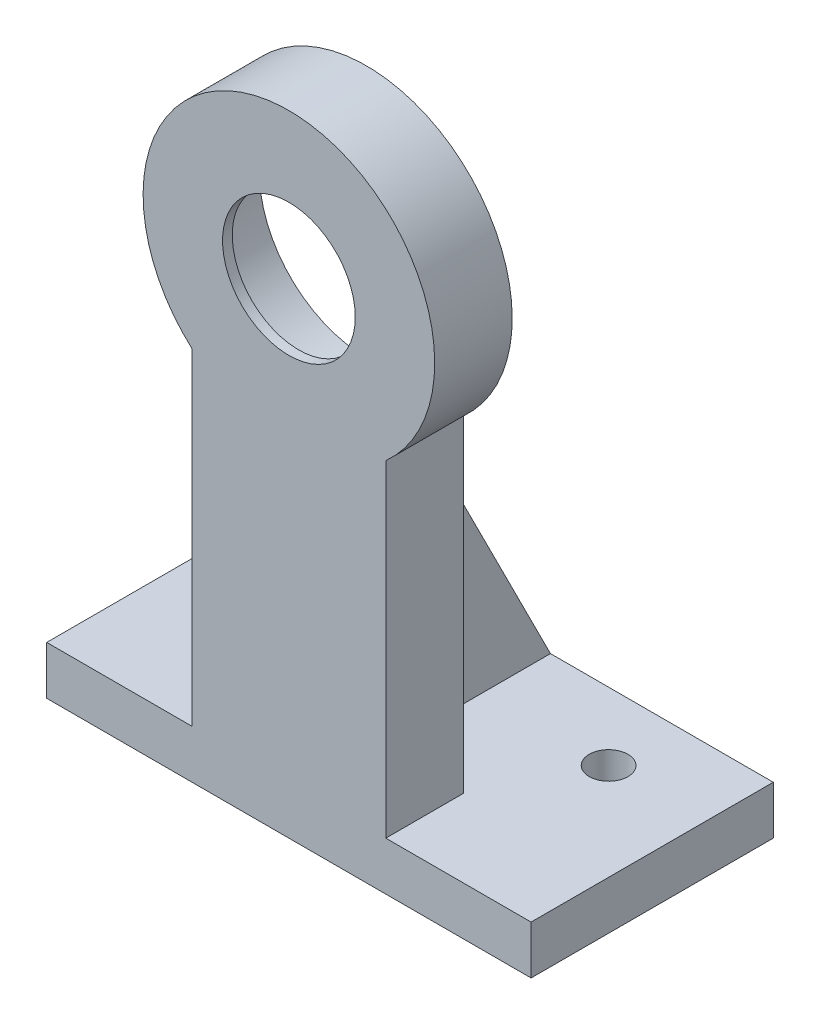
SolidWorks part; units mm, degrees
ref_plane "Front Plane" through (0, 0, 0) normal (0, 0, 1) x (1, 0, 0)
ref_plane "Top Plane" through (0, 0, 0) normal (0, 1, 0) x (1, 0, 0)
ref_plane "Right Plane" through (0, 0, 0) normal (1, 0, 0) x (0, 0, -1)
sketch "Sketch1" plane through (0, 0, 0) normal (0, 0, 1) x (1, 0, 0)
  line L1 (-10, 0) -> (10, 0)
  line L2 (-10, 0) -> (-10, -50)
  line L3 (-10, -50) -> (10, -50)
  line L4 (10, 0) -> (10, -50)
  circle A0 centre (0, 0) radius 11.05
  circle A1 centre (0, 0) radius 6.848
  circle A2 centre (0, 0) radius 15.05
  point P9 (0, 0)
  dimension "D1" = 22.1
  dimension "D2" = 13.6959
  dimension "D3" = 4
  dimension "D4" = 20
  dimension "D5" = 0
  dimension "D6" = 50
extrude "Boss-Extrude1" add sketch "Sketch1" along normal blind 8 contours A2 L2 L3 L4 | L4 A2 L2 A0 | L2 A2 L4 A0 | A1 L1 L2 A0 L4 | A1 L1 L4 A0 L2 region at (0, 7.1194, 0) region at (8.424, -0.2285, 0) region at (11.1744, -2.4957, 0) region at (0, -11.3558, 0) region at (0, -31.9102, 0)
extrude "Cut-Extrude1" cut sketch "Sketch1<3>" along normal blind 7 contours A1 L1 L4 A0 L2 | A1 L1 L2 A0 L4 region at (0, 7.1194, 0) region at (8.424, -0.2285, 0)
sketch "Sketch1<3>" plane through (0, 0, 0) normal (0, 0, 1) x (1, 0, 0) same geometry as "Sketch1"
sketch "Sketch2" plane through (0, -50, 0) normal (0, -1, 0) x (1, 0, 0)
  line L0 (-10, 8) -> (10, 8) construction
  line L1 (25, 8) -> (-25, 8)
  line L2 (25, 8) -> (25, -17)
  line L3 (25, -17) -> (-25, -17)
  line L4 (-25, 8) -> (-25, -17)
  circle A0 centre (-15, -10) radius 2
  circle A1 centre (15, -10) radius 2
  point P4 (0, -17)
  dimension "D5" = 4
  dimension "D6" = 4
  dimension "D1" = 50
  dimension "D2" = 0
  dimension "D3" = 25
  dimension "D4" = 0
  dimension "D7" = 7
  dimension "D8" = 7
  dimension "D9" = 30
  dimension "D10" = 15
extrude "Boss-Extrude2" add sketch "Sketch2" against normal blind 5
sketch "Sketch4" plane through (0, -45, 0) normal (0, 1, 0) x (1, 0, 0)
  line L0 (15.05, 0) -> (-15.05, 0) construction
  line L1 (-1.9092, 0) -> (2.0777, 0)
  line L2 (-1.9092, 0) -> (-1.9092, 17)
  line L3 (-1.9092, 17) -> (2.0777, 17)
  line L4 (2.0777, 0) -> (2.0777, 17)
  line L5 (-25, 17) -> (25, 17) construction
sketch "Sketch5" plane through (0, 0, 0) normal (1, 0, 0) x (0, 0, -1)
  line L0 (0, -11.2473) -> (17, -45)
  line L1 (17, -45) -> (0, -45)
  line L2 (0, -45) -> (17, -45) construction
  line L3 (0, -45) -> (-8, -45) construction
  line L4 (0, -45) -> (0, -11.2473)
extrude "Boss-Extrude3" add sketch "Sketch5" along normal blind 2 and the other way blind 2
